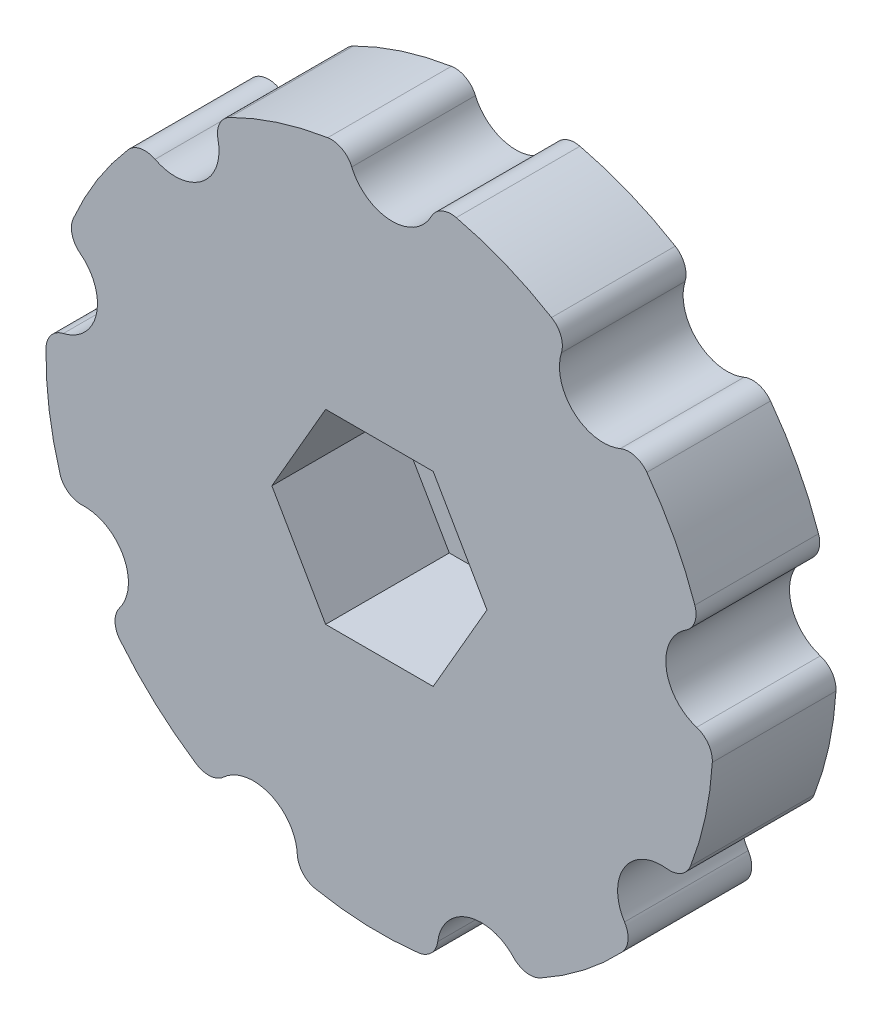
SolidWorks part; units mm, degrees
ref_plane "Alzado" through (0, 0, 0) normal (0, 0, 1) x (1, 0, 0)
ref_plane "Planta" through (0, 0, 0) normal (0, 1, 0) x (1, 0, 0)
ref_plane "Vista lateral" through (0, 0, 0) normal (1, 0, 0) x (0, 0, -1)
sketch "Croquis1" plane through (0, 0, 0) normal (0, 0, 1) x (1, 0, 0)
  arc A1 (-1.8551, 21.2106) -> (3.481, 21.0051) centre (0.8612, 22.3613) ccw
  arc A2 (12.2128, 17.4407) -> (16.1684, 13.8533) centre (15.0332, 16.5761) ccw
  arc A3 (20.5662, 5.5101) -> (21.2904, 0.2194) centre (22.1711, 3.0349) ccw
  arc A4 (19.2965, -8.9987) -> (16.4504, -13.5171) centre (18.9348, -11.9264) ccw
  arc A5 (8.9977, -19.2969) -> (3.9131, -20.9289) centre (6.8387, -21.3072) ccw
  arc A6 (-5.5112, -20.5659) -> (-10.4552, -18.5477) centre (-8.4573, -20.7182) ccw
  arc A7 (-17.4413, -12.2119) -> (-19.9314, -7.4879) centre (-19.796, -10.4348) ccw
  arc A8 (-21.2105, 1.8562) -> (-20.0815, 7.0756) centre (-21.872, 4.7311) ccw
  arc A9 (-15.055, 15.0558) -> (-10.8352, 18.3283) centre (-13.7138, 17.6833) ccw
  arc A10 (-22.3738, 0.4228) -> (-21.4372, -6.4198) centre (0, 0) ccw
  arc A11 (-16.8676, 14.7055) -> (-20.5484, 8.8617) centre (0, 0) ccw
  arc A12 (-17.4111, -14.0578) -> (-12.2953, -18.6974) centre (0, 0) ccw
  arc A13 (-4.3015, -21.9605) -> (2.5998, -22.2263) centre (0, 0) ccw
  arc A14 (10.8208, -19.5877) -> (16.2783, -15.3552) centre (0, 0) ccw
  arc A15 (20.8799, -8.0496) -> (22.3401, -1.2993) centre (0, 0) ccw
  arc A16 (21.1691, 7.255) -> (17.9487, 13.3646) centre (0, 0) ccw
  arc A17 (11.553, 19.1649) -> (5.1589, 21.7751) centre (0, 0) ccw
  arc A18 (-3.4688, 22.1073) -> (-10.0448, 19.9967) centre (0, 0) ccw
  arc A19 (2.5998, -22.2263) -> (3.9131, -20.9289) centre (2.4255, -20.7365) ccw
  arc A20 (10.8208, -19.5877) -> (8.9977, -19.2969) centre (10.0955, -18.2747) cw
  arc A21 (16.2783, -15.3552) -> (16.4504, -13.5171) centre (15.1872, -14.326) ccw
  arc A22 (20.8799, -8.0496) -> (19.2965, -8.9987) centre (19.4803, -7.51) cw
  arc A23 (22.3401, -1.2993) -> (21.2904, 0.2194) centre (20.8426, -1.2122) ccw
  arc A24 (20.5662, 5.5101) -> (21.1691, 7.255) centre (19.7501, 6.7687) ccw
  arc A25 (17.9487, 13.3646) -> (16.1684, 13.8533) centre (16.7455, 12.4688) ccw
  arc A26 (12.2128, 17.4407) -> (11.553, 19.1649) centre (10.7786, 17.8803) ccw
  arc A27 (5.1589, 21.7751) -> (3.481, 21.0051) centre (4.8131, 20.3155) ccw
  arc A28 (-1.8551, 21.2106) -> (-3.4688, 22.1073) centre (-3.2363, 20.6255) ccw
  arc A29 (-10.8352, 18.3283) -> (-10.0448, 19.9967) centre (-9.3715, 18.6563) cw
  arc A30 (-16.8676, 14.7055) -> (-15.055, 15.0558) centre (-15.737, 13.7198) cw
  arc A31 (-20.0815, 7.0756) -> (-20.5484, 8.8617) centre (-19.1711, 8.2677) cw
  arc A32 (-10.4552, -18.5477) -> (-12.2953, -18.6974) centre (-11.4711, -17.4441) cw
  arc A33 (-17.4413, -12.2119) -> (-17.4111, -14.0578) centre (-16.244, -13.1155) ccw
  arc A34 (-19.9314, -7.4879) -> (-21.4372, -6.4198) centre (-20.0002, -5.9895) cw
  arc A35 (-22.3738, 0.4228) -> (-21.2105, 1.8562) centre (-20.8741, 0.3944) cw
  arc A36 (-4.3015, -21.9605) -> (-5.5112, -20.5659) centre (-4.0132, -20.4885) cw
  circle A37 centre (0, 0) radius 2.2
  point P24 (0, 0)
  point P35 (9.5821, -20.2225)
  point P40 (20.3391, -9.3321)
  point P49 (12.7222, 18.4096)
  point P54 (-2.0877, 22.2802)
  point P59 (-15.9207, 15.7257)
  point P66 (-18.2514, -12.9481)
  point P73 (-5.6585, -21.6506)
  point P75 (0, 0)
  dimension "D1" = 22.3778
  dimension "D2" = 5.9
  dimension "D5" = 1.5
  dimension "D6" = 1.5
  dimension "D7" = 4.4
  dimension "D4" = 15.3073
  dimension "D3" = 9
extrude "Saliente-Extruir1" add sketch "Croquis1" along normal blind 8.3 contours A36 A6 A32 A12 A33 A7 A34 A10 A35 A8 A31 A11 A30 A9 A29 A18 A28 A1 A27 A17 A26 A2 A25 A16 A24 A3 A23 A15 A22 A4 A21 A14 A20 A5 A19 A13 | A37
sketch "Croquis2" plane through (0, 0, 8.3) normal (0, 0, 1) x (1, 0, 0)
  line L1 (7.2169, 0) -> (3.6084, 6.25)
  line L2 (3.6084, 6.25) -> (-3.6084, 6.25)
  line L3 (-3.6084, 6.25) -> (-7.2169, 0)
  line L4 (-7.2169, 0) -> (-3.6084, -6.25)
  line L5 (-3.6084, -6.25) -> (3.6084, -6.25)
  line L6 (3.6084, -6.25) -> (7.2169, 0)
  circle A0 centre (0, 0) radius 6.25 construction
  dimension "D1" = 12.5
extrude "Cortar-Extruir1" cut sketch "Croquis2" against normal blind 10
sketch "Croquis3" plane through (0, 0, 0) normal (0, 0, -1) x (-1, 0, 0)
  circle A0 centre (0, 0) radius 11.19
  circle A1 centre (0, 0) radius 2.2
  dimension "D1" = 22.38
  dimension "D2" = 4.4
extrude "Saliente-Extruir2" add sketch "Croquis3" along normal blind 3
fillet "Redondeo1" radius 10 1 edges at (11.19, 0, 0)
fillet "Redondeo2" radius 10 1 edges at (-11.19, 0, -3)
